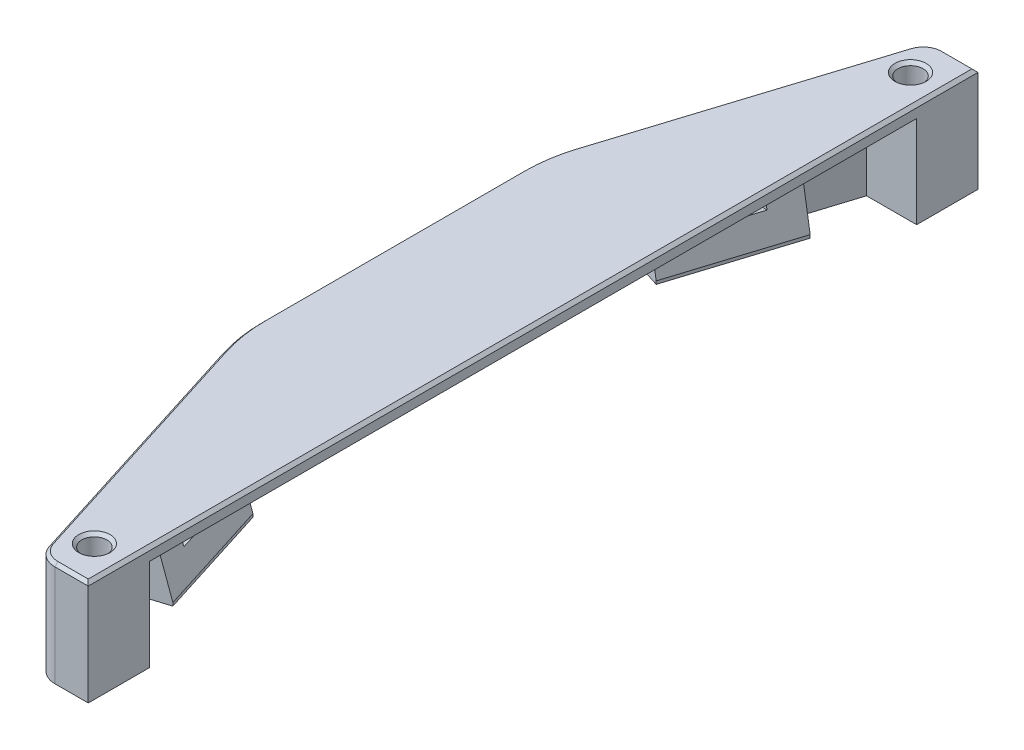
SolidWorks part; units mm, degrees
ref_plane "Спереди" through (0, 0, 0) normal (0, 0, 1) x (1, 0, 0)
ref_plane "Сверху" through (0, 0, 0) normal (0, 1, 0) x (1, 0, 0)
ref_plane "Справа" through (0, 0, 0) normal (1, 0, 0) x (0, 0, -1)
sketch "Эскиз17" plane through (0, 0, 0) normal (0, 1, 0) x (1, 0, 0)
  line L0 (67.6548, 0) -> (101.8569, 0) construction
  line L1 (101.8569, 0) -> (-162.377, 0) construction
  line L2 (0, -50) -> (0, 50)
  line L3 (0, 50) -> (30, 145)
  line L4 (30, 145) -> (46, 145)
  line L6 (30, -145) -> (46, -145)
  line L7 (0, -50) -> (30, -145)
  line L8 (46, 145) -> (46, 125)
  line L10 (6, 50) -> (6, -50)
  line L11 (46, -145) -> (46, -125)
  line L13 (6, 50) -> (29.6842, 125)
  line L14 (29.6842, 125) -> (46, 125)
  line L15 (29.6842, -125) -> (46, -125)
  line L16 (6, -50) -> (29.6842, -125)
  point P10 (46, 0)
  point P12 (0, 0)
  point P17 (6, 0)
  dimension "D1" = 290
  dimension "D2" = 100
  dimension "D3" = 20
  dimension "D4" = 16
  dimension "D5" = 100
  dimension "D6" = 6
extrude "Бобышка-Вытянуть10" add sketch "Эскиз17" along normal blind 30
sketch "Эскиз18" plane through (0, 30, 0) normal (0, 1, 0) x (1, 0, 0)
  line L0 (30, 145) -> (0, 50)
  line L1 (0, 50) -> (0, -50)
  line L2 (0, -50) -> (30, -145)
  line L3 (30, -145) -> (46, -145)
  line L4 (46, -145) -> (46, 145)
  line L5 (46, 145) -> (30, 145)
extrude "Бобышка-Вытянуть11" add sketch "Эскиз18" along normal blind 4
fillet "Скругление1" radius 50 2 edges at (0, 17, -50) (0, 17, 50)
fillet "Скругление2" radius 7 2 edges at (30, 17, 145) (30, 17, -145)
sketch "Эскиз20" plane through (0, 0, 0) normal (-1, 0, 0) x (0, 0, 1)
  line L0 (0, -3.7789) -> (0, 62.6022) construction
  line L2 (-35, 0) -> (35, 0)
  line L3 (-35, 0) -> (-35, 34)
  line L4 (-35, 34) -> (35, 34)
  line L5 (35, 0) -> (35, 34)
  line L6 (0, 34) -> (0, 0) construction
  line L7 (-35, 17) -> (35, 17) construction
  line L9 (-42.2928, 34) -> (42.2928, 34) construction
  line L10 (-42.2928, 0) -> (42.2928, 0) construction
  point P3 (0, 17)
  dimension "D1" = 70
extrude "Бобышка-Вытянуть12" add sketch "Эскиз20" against normal blind 10
sketch "Эскиз19" plane through (10, 0, 0) normal (1, 0, 0) x (0, 0, -1)
  line L0 (0, 82.949) -> (0, -29.4108) construction
  circle A0 centre (-11, 15) radius 8.25
  circle A1 centre (11, 15) radius 8.25
  dimension "D1" = 16.5
  dimension "D2" = 11
  dimension "D3" = 15
extrude "Вырез-Вытянуть1" cut sketch "Эскиз19" against normal blind 8
sketch "Эскиз21" plane through (10, 0, 0) normal (1, 0, 0) x (0, 0, -1)
  line L0 (0, 66.014) -> (0, -7.0436) construction
  circle A0 centre (-11, 15) radius 7
  circle A1 centre (11, 15) radius 7
  dimension "D1" = 14
extrude "Вырез-Вытянуть2" cut sketch "Эскиз21" against normal through all
chamfer "Фаска1" distance 1 angle 45 2 edges at (10, 15, -2.75) (10, 15, 2.75)
sketch "Эскиз23" plane through (0, 0, 0) normal (0, -1, 0) x (1, 0, 0)
  line L0 (23.8647, -106.5717) -> (11.8195, -68.4283)
  line L1 (6, -50) -> (29.6842, -125) construction
  line L2 (11.8195, -68.4283) -> (20.4017, -65.7182)
  line L3 (20.4017, -65.7182) -> (32.447, -103.8615)
  line L4 (17.8421, -87.5) -> (67.4, -71.8501) construction
  line L5 (23.8647, -106.5717) -> (32.447, -103.8615)
  line L6 (17.8421, 87.5) -> (61.11, 73.8364) construction
  line L7 (29.6842, 125) -> (6, 50) construction
  line L8 (11.8195, 68.4283) -> (23.8647, 106.5717)
  line L9 (29.6842, 125) -> (6, 50) construction
  line L10 (23.8647, 106.5717) -> (32.447, 103.8615)
  line L11 (32.447, 103.8615) -> (20.4017, 65.7182)
  line L12 (11.8195, 68.4283) -> (20.4017, 65.7182)
  point P9 (26.4243, -84.7898)
  point P19 (26.4243, 84.7898)
  dimension "D1" = 9
  dimension "D2" = 40
  dimension "D3" = 9
  dimension "D4" = 40
extrude "Бобышка-Вытянуть13" add sketch "Эскиз23" against normal blind 1
chamfer "Фаска2" distance 9 angle 75 2 edges at (17.8421, 1, -87.5) (17.8421, 1, 87.5) first distance on face at (22.1332, 1, -86.1449) first distance on face at (22.1332, 1, 86.1449)
sketch "Эскиз24" plane through (-0.0597, -0.0168, -0.0189) normal (0.9211, 0.2588, 0.2909) x (0.28, 0.0787, -0.9568)
  line L0 (88.6019, -6.1855) -> (91.9427, 34.6898) construction
  line L1 (108.5354, -7.8147) -> (68.6684, -4.5563) construction
  line L2 (99.9155, 9.479) -> (70.6711, 11.8693) construction
  line L3 (79.7784, 8.6166) -> (99.7119, 6.9873)
  line L4 (79.7784, 8.6166) -> (79.371, 3.6332)
  line L5 (99.7119, 6.9873) -> (99.3046, 2.004)
  line L6 (79.371, 3.6332) -> (99.3046, 2.004)
  line L7 (79.7784, 8.6166) -> (99.3046, 2.004) construction
  line L8 (99.7119, 6.9873) -> (79.371, 3.6332) construction
  line L9 (108.4567, -8.7774) -> (68.5897, -5.519) construction
  circle A0 centre (90.1117, 12.287) radius 3
  circle A1 centre (99.9155, 9.479) radius 1.4
  circle A3 centre (79.982, 11.1083) radius 1.4
  point P13 (89.5415, 5.3103)
  dimension "D1" = 2
  dimension "D2" = 6
  dimension "D3" = 2.8
  dimension "D4" = 10
  dimension "D5" = 10
  dimension "D6" = 5
  dimension "D7" = 20
  dimension "D8" = 2.5
  dimension "D9" = 10
extrude "Вырез-Вытянуть3" cut sketch "Эскиз24" against normal through all contours A0 region at (21.85, 18.9025, -86.2343)
extrude "Вырез-Вытянуть4" cut sketch "Эскиз24<3>" against normal blind 7 contours A1 | A3 region at (25.355, 16.9707, -95.6143) region at (19.3323, 16.9707, -76.5426)
sketch "Эскиз24<3>" plane through (-0.0597, -0.0168, -0.0189) normal (0.9211, 0.2588, 0.2909) x (0.28, 0.0787, -0.9568) same geometry as "Эскиз24"
extrude "Вырез-Вытянуть5" cut sketch "Эскиз24<4>" against normal blind 2.5 contours L4 L6 L5 L3 region at (23.5777, 12.1411, -85.6888)
sketch "Эскиз24<4>" plane through (-0.0597, -0.0168, -0.0189) normal (0.9211, 0.2588, 0.2909) x (0.28, 0.0787, -0.9568) same geometry as "Эскиз24"
draft "Уклон1" type of draft neutral plane draft angle 35 faces to draft 1 face at (22.7534, 18.9025, -89.0951) neutral plane through (6, 34.5885, -50) neutral plane normal (0.9211, 0.2588, 0.2909) reverse direction yes parameters "D1"=35
sketch "Эскиз25" plane through (-0.0597, -0.0168, 0.0189) normal (0.9211, 0.2588, -0.2909) x (-0.28, -0.0787, -0.9568)
  line L0 (-88.6019, -6.1855) -> (-91.6172, 30.7066) construction
  line L1 (-68.6684, -4.5563) -> (-108.5354, -7.8147) construction
  line L2 (-97.0705, 9.7116) -> (-75.836, 11.4471) construction
  line L3 (-99.3046, 2.004) -> (-99.7119, 6.9873)
  line L4 (-99.3046, 2.004) -> (-79.371, 3.6332)
  line L5 (-99.7119, 6.9873) -> (-79.7784, 8.6166)
  line L6 (-79.371, 3.6332) -> (-79.7784, 8.6166)
  line L7 (-99.3046, 2.004) -> (-79.7784, 8.6166) construction
  line L8 (-99.7119, 6.9873) -> (-79.371, 3.6332) construction
  line L9 (-68.5897, -5.519) -> (-108.4567, -8.7774) construction
  circle A0 centre (-90.1524, 12.7853) radius 3
  circle A1 centre (-79.982, 11.1083) radius 1.4
  circle A2 centre (-99.9155, 9.479) radius 1.4
  point P13 (-89.5415, 5.3103)
  dimension "D1" = 6
  dimension "D2" = 20
  dimension "D3" = 2.5
  dimension "D6" = 2.8
  dimension "D4" = 2.5
  dimension "D5" = 10
extrude "Вырез-Вытянуть6" cut sketch "Эскиз25" against normal through all contours A0 region at (21.7266, 19.3855, 86.2733)
extrude "Вырез-Вытянуть7" cut sketch "Эскиз25<3>" against normal blind 7 contours A1 | A2 region at (19.3323, 16.9707, 76.5426) region at (25.355, 16.9707, 95.6143)
sketch "Эскиз25<3>" plane through (-0.0597, -0.0168, 0.0189) normal (0.9211, 0.2588, -0.2909) x (-0.28, -0.0787, -0.9568) same geometry as "Эскиз25"
extrude "Вырез-Вытянуть8" cut sketch "Эскиз25<4>" against normal blind 2.5 contours L4 L6 L5 L3 region at (23.5777, 12.1411, 85.6888)
sketch "Эскиз25<4>" plane through (-0.0597, -0.0168, 0.0189) normal (0.9211, 0.2588, -0.2909) x (-0.28, -0.0787, -0.9568) same geometry as "Эскиз25"
draft "Уклон2" type of draft neutral plane draft angle 35 faces to draft 1 face at (20.8232, 19.3855, 83.4126) neutral plane through (6, 34.5885, 50) neutral plane normal (0.9211, 0.2588, -0.2909) reverse direction yes parameters "D1"=35
chamfer "Фаска3" distance 1 angle 45 10 edges at (0.5836, 34, -49.91) (15.388, 34, -98.7287) (30.9923, 34, -143.646) (40.5651, 34, -145) (46, 34, 0) (40.5651, 34, 145) (30.9923, 34, 143.646) (15.388, 34, 98.7287) (0.5836, 34, 49.91) (0, 34, 0)
sketch "Эскиз26" plane through (0, 34, 0) normal (0, 1, 0) x (1, 0, 0)
  line L0 (-24.307, 0) -> (93.4127, 0) construction
  line L1 (46, 145) -> (46, -145) construction
  line L2 (35.1302, 145) -> (46, 145) construction
  circle A0 centre (36, 133) radius 2.4
  circle A1 centre (36, -133) radius 2.4
  dimension "D1" = 4.8
  dimension "D2" = 10
  dimension "D3" = 12
extrude "Вырез-Вытянуть9" cut sketch "Эскиз26" against normal through all
sketch "Эскиз27" plane through (0, 34, 0) normal (0, 1, 0) x (1, 0, 0)
  circle A0 centre (36, 133) radius 4.1
  circle A1 centre (36, -133) radius 4.1
  dimension "D1" = 8.2
extrude "Вырез-Вытянуть10" cut sketch "Эскиз27" against normal blind 32
chamfer "Фаска4" distance 2 angle 45 2 edges at (36, 2, 137.1) (36, 2, -128.9)
chamfer "Фаска5" distance 1 angle 45 2 edges at (36, 34, -128.9) (36, 34, 137.1)
